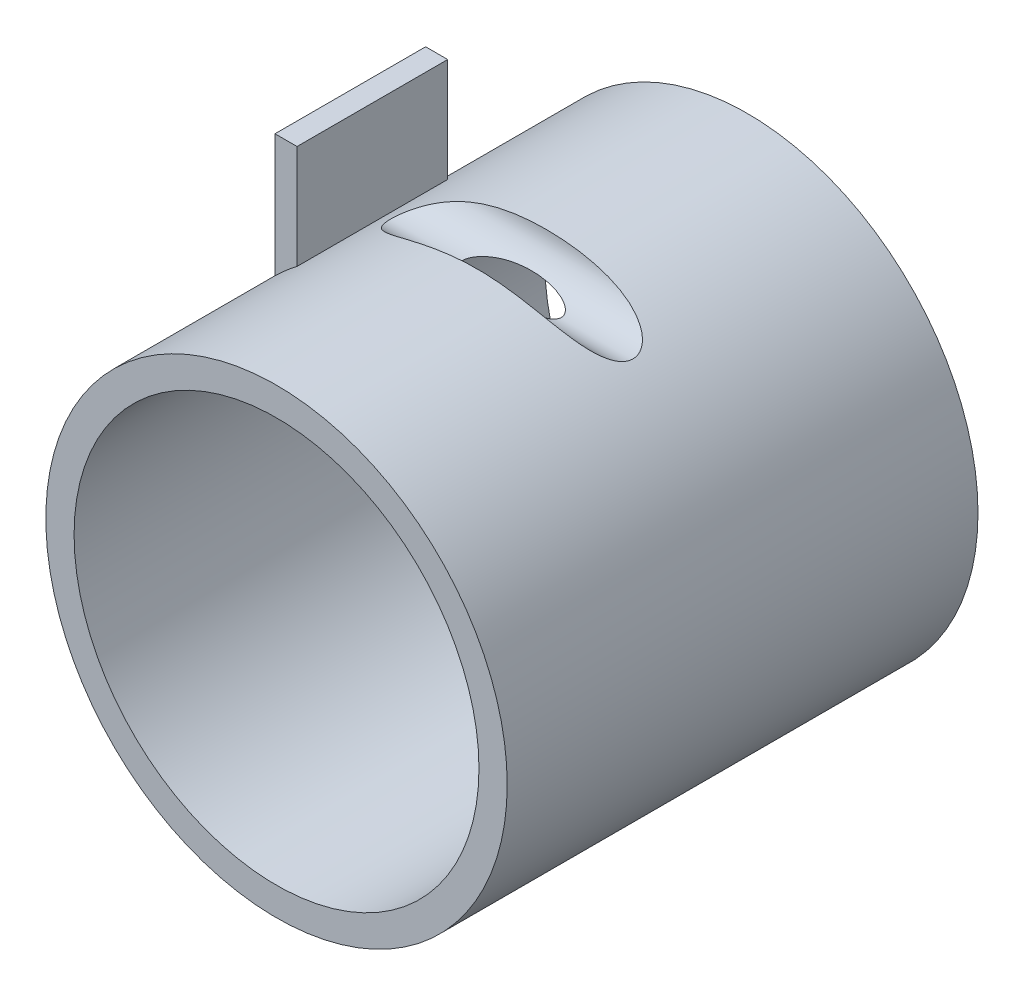
SolidWorks part; units mm, degrees
ref_plane "Front Plane" through (0, 0, 0) normal (0, 0, 1) x (1, 0, 0)
ref_plane "Top Plane" through (0, 0, 0) normal (0, 1, 0) x (1, 0, 0)
ref_plane "Right Plane" through (0, 0, 0) normal (1, 0, 0) x (0, 0, -1)
sketch "Sketch1" plane through (0, 0, 0) normal (0, 0, 1) x (1, 0, 0)
  circle A0 centre (0, 0) radius 21.5
  circle A1 centre (0, 0) radius 24.5
  dimension "D1" = 43
  dimension "D2" = 3
extrude "Boss-Extrude1" add sketch "Sketch1" along normal blind 50
ref_plane "Plane1" through (0, 0, 25) normal (0, 0, 1) x (1, 0, 0)
sketch "Sketch3" plane through (0, 0, 0) normal (1, 0, 0) x (0, 0, -1)
  line L0 (0, 24.5) -> (-50, 24.5) construction
  circle A0 centre (-25, 24.5) radius 3.65
  dimension "D1" = 7.3
extrude "Cut-Extrude1" cut sketch "Sketch3" against normal mid plane 50
sketch "Sketch4" plane through (0, 0, 25) normal (0, 0, 1) x (1, 0, 0)
  line L3 (0, 0) -> (50000, 0) construction
  line L4 (-19.776, 24.5) -> (49980.224, 24.5) construction
  line L5 (-14.8202, 19.5093) -> (-14.8202, 30.5416)
  line L6 (-17.1635, 17.4833) -> (-17.1635, 30.5416)
  line L7 (-17.1635, 30.5416) -> (-14.8202, 30.5416)
  line L8 (0, 0) -> (0, 11.0861) construction
  circle A3 centre (0, 0) radius 24.5 construction
  arc A4 (-14.8202, 19.5093) -> (-17.1635, 17.4833) centre (0, 0) ccw
extrude "Boss-Extrude2" add sketch "Sketch4" along normal mid plane 16
